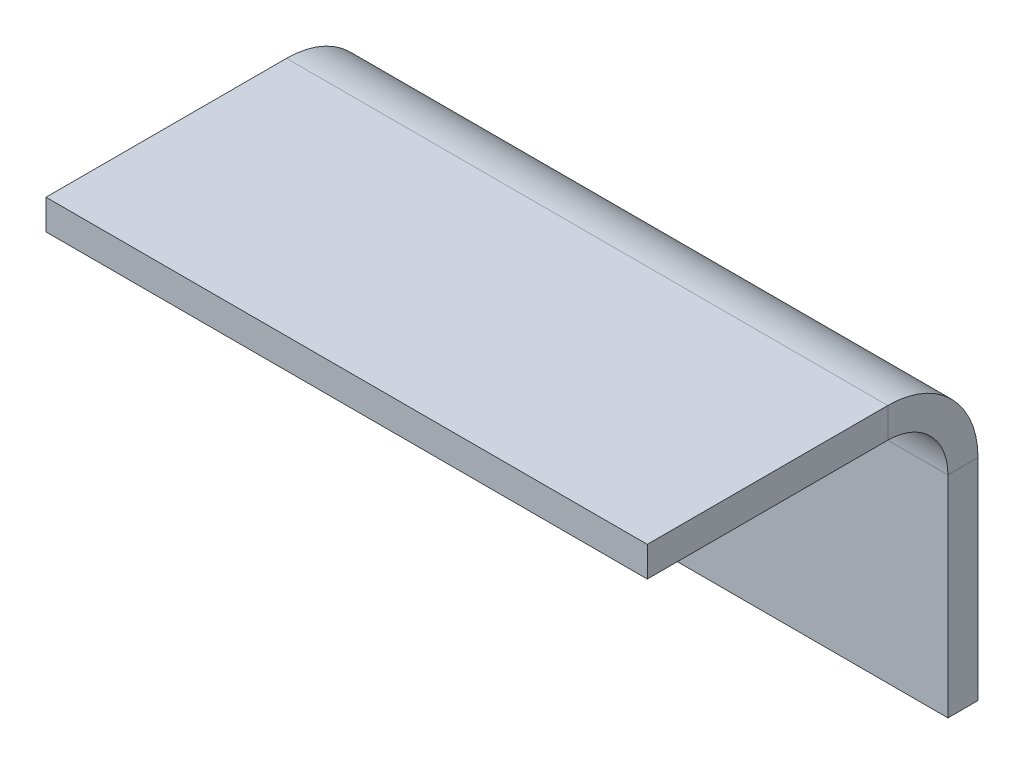
SolidWorks part; units mm, degrees
note: The reader was unsure of these and kept them because the rebuilt part matched: flange length of "EdgeFlange".
ref_plane "前视基准面" through (0, 0, 0) normal (0, 0, 1) x (1, 0, 0)
ref_plane "上视基准面" through (0, 0, 0) normal (0, 1, 0) x (1, 0, 0)
ref_plane "右视基准面" through (0, 0, 0) normal (1, 0, 0) x (0, 0, -1)
other "Configuration Table"
sketch "草图1" plane through (0, 0, 0) normal (0, 0, 1) x (1, 0, 0)
  line L1 (0, 0) -> (20, 0)
  line L2 (0, 0) -> (0, 10)
  line L3 (0, 10) -> (20, 10)
  line L4 (20, 0) -> (20, 10)
base flange "BasePlate" sketch "草图1" thickness 1 reverse thickness direction no parameters "D1"=2
sketch "草图9" plane through (0, 10, 0) normal (0, 1, 0) x (-1, 0, 0)
  line L0 (-20, 0) -> (0, 0) construction
  line L1 (-20, 0) -> (0, 0)
  line L2 (-20, 0) -> (-20, 10)
  line L3 (-20, 10) -> (-18, 10)
  line L4 (-18, 10) -> (-2, 10)
  line L5 (-2, 10) -> (0, 10)
  line L6 (0, 0) -> (0, 10)
edge flange "EdgeFlange" sketch "草图9" flange angle 90 flange length 10 flange position material inside bend radius 2 thickness 1 relief rectangular parameters "D6"=10
bend "边线折弯1" bend radius 2 bend angle 90 parameters "D5"=1
sketch "折弯-线1" plane through (0, 0, 0) normal (0, 1, 0) x (1, 0, 0)
sketch "边界框1" plane through (0, 0, 0) normal (0, 1, 0) x (1, 0, 0)
sheet metal parameters "钣金6" thickness 1 parameters "D1"=2
flat pattern "平板型式6" [suppressed]
sketch "折弯-线2" plane through (0, 0, 0) normal (0, 1, 0) x (1, 0, 0)
sketch "边界框2" [suppressed] plane through (0, 0, 0) normal (0, 1, 0) x (1, 0, 0)
sheet metal parameters "钣金7" thickness 1 parameters "D1"=2
flat pattern "平板型式6" [suppressed]
sketch "折弯-线2" plane through (0, 0, 0) normal (0, 1, 0) x (1, 0, 0)
sketch "边界框2" [suppressed] plane through (0, 0, 0) normal (0, 1, 0) x (1, 0, 0)
bend of the flat pattern "展平-<边线折弯1>1"
